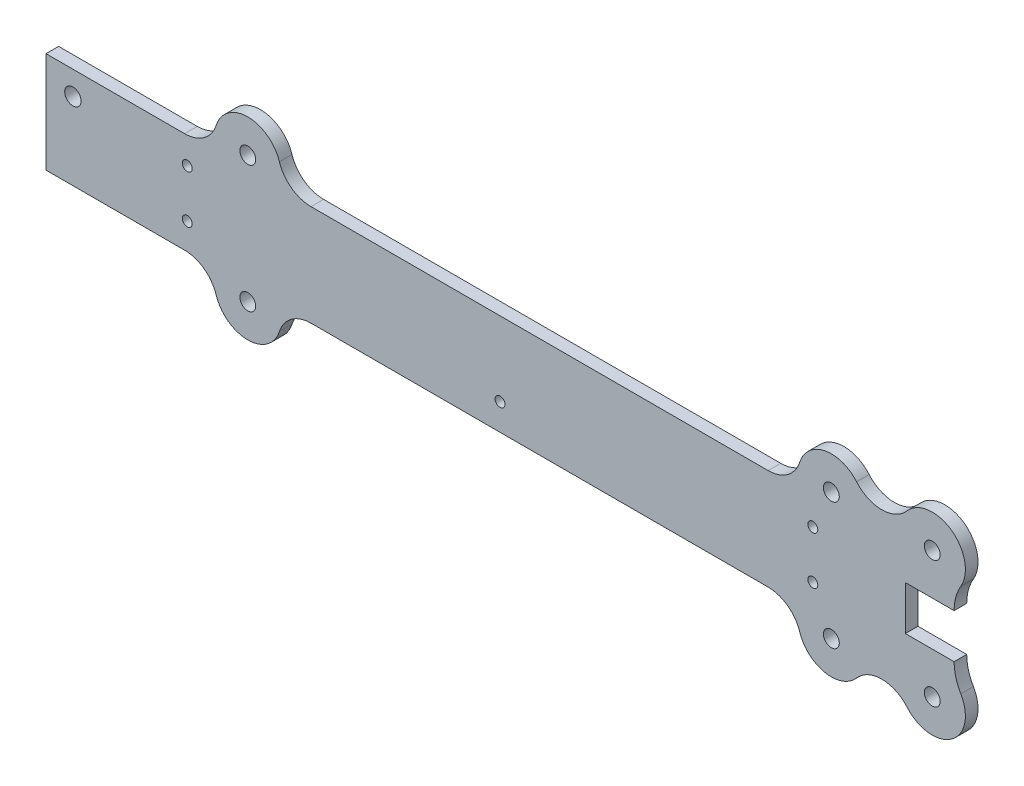
SolidWorks part; units mm, degrees
ref_plane "Front Plane" through (0, 0, 0) normal (0, 0, 1) x (1, 0, 0)
ref_plane "Top Plane" through (0, 0, 0) normal (0, 1, 0) x (1, 0, 0)
ref_plane "Right Plane" through (0, 0, 0) normal (1, 0, 0) x (0, 0, -1)
sketch "Sketch1" plane through (0, 0, 0) normal (0, 0, 1) x (1, 0, 0)
  line L0 (457.2, 14.28) -> (457.2, 6.0254) construction
  line L1 (0, 50.8) -> (69.7828, 50.8)
  line L2 (0, 50.8) -> (0, 0)
  line L3 (0, 0) -> (69.7828, 0)
  line L4 (457.2, 44.7746) -> (457.2, 36.52) construction
  line L5 (432.66, 36.52) -> (457.2, 36.52)
  line L6 (432.66, 36.52) -> (432.66, 14.28)
  line L7 (432.66, 14.28) -> (457.2, 14.28)
  line L8 (101.6, 57.34) -> (101.6, 83.1732) construction
  line L9 (133.4172, 50.8) -> (363.5828, 50.8)
  line L10 (0, 25.4) -> (457.2, 25.4) construction
  line L12 (0, 25.4) -> (457.2, 25.4) construction
  line L13 (133.4172, 0) -> (363.5828, 0)
  circle A0 centre (13.54, 38.94) radius 4 construction
  circle A1 centre (13.54, 38.94) radius 4.127
  circle A2 centre (101.6, -6.54) radius 4
  arc A3 (133.4172, 0) -> (117.5086, -11.62) centre (133.4172, -16.7) ccw
  arc A4 (69.7828, 0) -> (85.6914, -11.62) centre (69.7828, -16.7) cw
  arc A5 (117.5086, -11.62) -> (85.6914, -11.62) centre (101.6, -6.54) cw
  arc A6 (460.5711, 48.8335) -> (433.5, 68.1844) centre (446.2, 57.34) ccw
  circle A7 centre (386.08, 13.3425) radius 2.4892 construction
  circle A8 centre (386.08, 37.4575) radius 2.4892 construction
  circle A9 centre (228.6, 13.3425) radius 2.4892 construction
  circle A10 centre (71.12, 13.3425) radius 2.4892 construction
  circle A11 centre (71.12, 37.4575) radius 2.4892 construction
  circle A12 centre (386.08, 13.3425) radius 2.4892
  circle A13 centre (386.08, 37.4575) radius 2.4892
  circle A14 centre (228.6, 13.3425) radius 2.4892
  circle A15 centre (71.12, 13.3425) radius 2.4892
  circle A16 centre (71.12, 37.4575) radius 2.4892
  circle A17 centre (101.6, 57.34) radius 4
  arc A18 (117.5086, 62.42) -> (85.6914, 62.42) centre (101.6, 57.34) ccw
  arc A19 (69.7828, 50.8) -> (85.6914, 62.42) centre (69.7828, 67.5) ccw
  circle A20 centre (101.6, 57.34) radius 11 construction
  arc A21 (133.4172, 50.8) -> (117.5086, 62.42) centre (133.4172, 67.5) cw
  circle A22 centre (101.6, 57.34) radius 16.7 construction
  arc A23 (408.1, 68.1844) -> (379.4914, 62.42) centre (395.4, 57.34) ccw
  circle A24 centre (395.4, 57.34) radius 4
  circle A25 centre (446.2, 57.34) radius 4
  circle A26 centre (395.4, 57.34) radius 11 construction
  arc A27 (460.5711, 1.9665) -> (433.5, -17.3844) centre (446.2, -6.54) cw
  circle A28 centre (446.2, -6.54) radius 4
  circle A29 centre (395.4, -6.54) radius 4
  arc A30 (408.1, -17.3844) -> (379.4914, -11.62) centre (395.4, -6.54) cw
  arc A31 (408.1, 68.1844) -> (433.5, 68.1844) centre (420.8, 79.0287) ccw
  arc A32 (408.1, -17.3844) -> (433.5, -17.3844) centre (420.8, -28.2287) cw
  arc A33 (363.5828, 50.8) -> (379.4914, 62.42) centre (363.5828, 67.5) ccw
  arc A34 (363.5828, 0) -> (379.4914, -11.62) centre (363.5828, -16.7) cw
  arc A35 (457.2, 36.52) -> (460.5711, 48.8335) centre (481.3739, 36.52) cw
  arc A36 (457.2, 14.28) -> (460.5711, 1.9665) centre (481.3739, 14.28) ccw
  dimension "D1" = 8
  dimension "D3" = 8
  dimension "D2" = 0.127
  dimension "D4" = 12.7
extrude "Boss-Extrude1" add sketch "Sketch1" along normal blind 6.35
